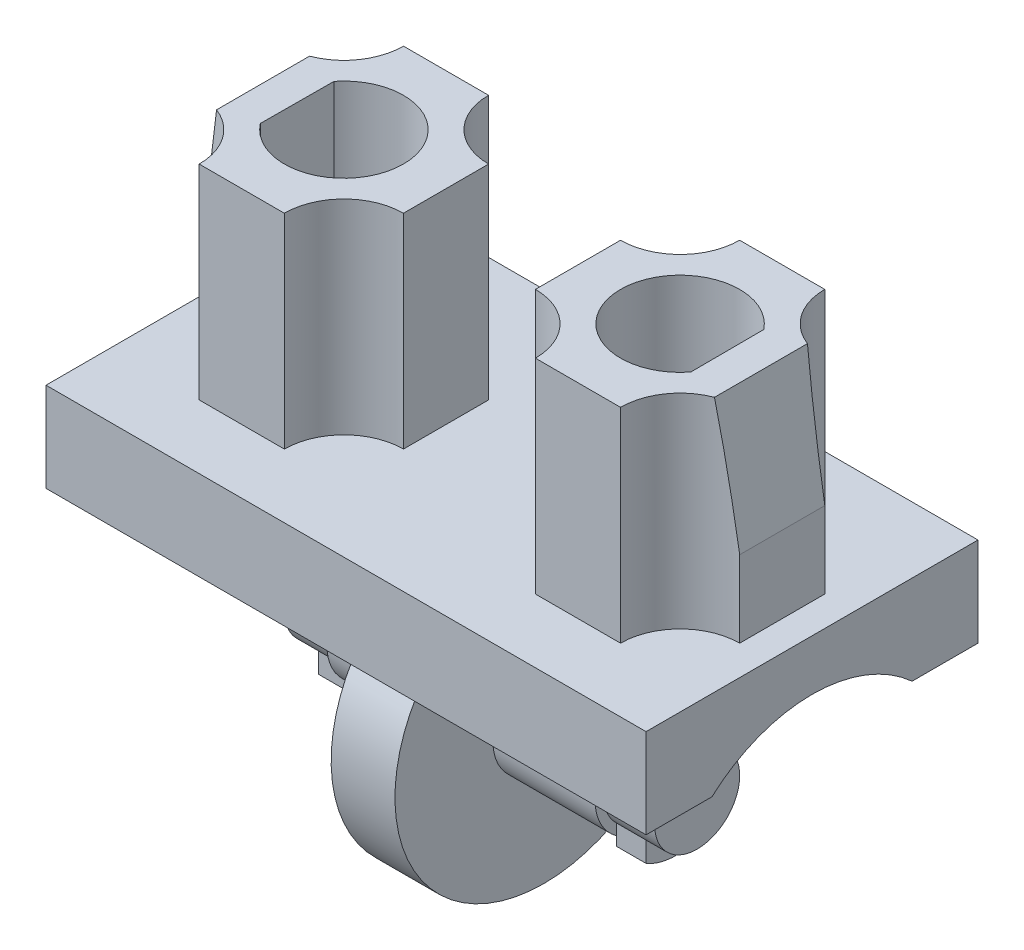
SolidWorks part; units mm, degrees
ref_plane "Front Plane" through (0, 0, 0) normal (0, 0, 1) x (1, 0, 0)
ref_plane "Top Plane" through (0, 0, 0) normal (0, 1, 0) x (1, 0, 0)
ref_plane "Right Plane" through (0, 0, 0) normal (1, 0, 0) x (0, 0, -1)
sketch "Sketch1" plane through (0, 0, 0) normal (1, 0, 0) x (0, 0, -1)
  line L0 (0, 0) -> (0, -4.7) construction
  line L1 (2.3513, -2.1074) -> (3.9, -2.1074)
  line L2 (-3.9, -2.1074) -> (-2.3513, -2.1074)
  line L3 (-3.9, -2.1074) -> (-3.9, -0.0074)
  line L4 (-3.9, -0.0074) -> (3.9, -0.0074)
  line L5 (3.9, -2.1074) -> (3.9, -0.0074)
  line L6 (-3.9, -2.1074) -> (3.9, -0.0074) construction
  line L7 (-3.9, -0.0074) -> (3.9, -2.1074) construction
  circle A0 centre (0, -4.7) radius 3.5
  point P3 (0, -1.0574)
  point P9 (0, -0.9349)
  point P10 (0, -4.7)
  dimension "D2" = 7
  dimension "D1" = 4.7
  dimension "D3" = 7.8
  dimension "D4" = 2.1
extrude "Hip Base - Extruded Boss/Base" add sketch "Sketch1" along normal mid plane 14.1 contours A0 L1 L5 L4 L3 L2 region at (0, -0.9088, 0)
extrude "Leg Joint - Extruded Boss/Base" add sketch "Sketch1<3>" along normal mid plane 1.5 contours A0 region at (0, -4.7, 0)
sketch "Sketch1<3>" plane through (0, 0, 0) normal (1, 0, 0) x (0, 0, -1) same geometry as "Sketch1"
sketch "Sketch2" plane through (0.75, 0, 0) normal (1, 0, 0) x (0, 0, -1)
  circle A0 centre (0, -4.7) radius 1.2
  dimension "D1" = 2.4
extrude "Leg Peg - Extruded Boss/Base" add sketch "Sketch2" along normal blind 2.4
sketch "Sketch3" plane through (3.15, 0, 0) normal (1, 0, 0) x (0, 0, -1)
  line L0 (-0.6614, -3.95) -> (0.6614, -3.95)
  arc A0 (-0.6614, -3.95) -> (0.6614, -3.95) centre (0, -4.7) ccw
  dimension "D1" = 2
  dimension "D2" = 0.75
extrude "Leg Peg Inner - Extruded Boss/Base" add sketch "Sketch3" along normal blind 1.2
sketch "Sketch4" plane through (3.15, 0, 0) normal (1, 0, 0) x (0, 0, -1)
  line L2 (-0.7, -5.8893) -> (-0.7, -5.4141)
  line L4 (0.7, -5.8893) -> (0.7, -5.4141)
  arc A0 (-0.6614, -3.95) -> (0.6614, -3.95) centre (0, -4.7) ccw construction
  circle A1 centre (0, -4.7) radius 1.2
  arc A2 (-0.7, -5.6747) -> (0.7, -5.6747) centre (0, -4.7) ccw
  arc A3 (-0.7, -5.4141) -> (0.7, -5.4141) centre (0, -4.7) ccw
  arc A4 (-0.7, -5.8893) -> (0.7, -5.8893) centre (0, -4.7) ccw
  arc A5 (-0.6614, -3.95) -> (0.6614, -3.95) centre (0, -4.7) ccw construction
  arc A6 (-0.9128, -3.665) -> (0.9128, -3.665) centre (0, -4.7) ccw construction
  point P10 (0, 0)
  point P15 (0.7, -5.4313)
  dimension "D3" = 0.7
  dimension "D4" = 1.4
  dimension "D1" = 0
  dimension "D2" = 0.38
extrude "Leg Lock - Extruded Detail" add sketch "Sketch4" along normal blind 0.7 contours L2 A3 L4 A4
sketch "Sketch5" plane through (0, -0.0074, 0) normal (0, 1, 0) x (1, 0, 0)
  line L0 (0, 0) -> (7.05, 0) construction
  line L1 (7.05, -3.9) -> (7.05, 3.9) construction
  line L3 (1.55, -2.4) -> (6.35, -2.4)
  line L4 (1.55, -2.4) -> (1.55, 2.4)
  line L5 (1.55, 2.4) -> (6.35, 2.4)
  line L6 (6.35, -2.4) -> (6.35, 2.4)
  line L7 (1.55, -2.4) -> (6.35, 2.4) construction
  line L8 (1.55, 2.4) -> (6.35, -2.4) construction
  circle A0 centre (1.55, 2.4) radius 1.4
  circle A1 centre (6.35, 2.4) radius 1.4
  circle A2 centre (6.35, -2.4) radius 1.4
  circle A3 centre (1.55, -2.4) radius 1.4
  point P5 (3.95, 0)
  point P11 (0, 0)
  point P20 (3.95, 0)
  dimension "D4" = 2.8
  dimension "D1" = 1.55
  dimension "D2" = 4.8
  dimension "D3" = 4.8
  dimension "D5" = 4
extrude "Hip Peg - Extruded Boss/Base" add sketch "Sketch5" along normal blind 4.8 contours A3 L3 A2 L6 A1 L5 A0 L4 region at (3.95, -0.0074, 0)
sketch "Sketch6" plane through (0, 4.7926, 0) normal (0, 1, 0) x (1, 0, 0)
  line L0 (4.95, 2.4) -> (2.95, -2.4) construction
  line L1 (5.058, -0.8557) -> (5.05, 0.866)
  arc A0 (5.05, 0.866) -> (5.058, -0.8557) centre (3.95, 0) ccw
  point P8 (5.04, 0.8785)
  point P9 (4.95, -0.8705)
  point P10 (5.182, -0.8567)
  point P11 (5.04, -0.8785)
  dimension "D1" = 2.8
  dimension "D2" = 1.3
extrude "Hip Cavity - Extruded Cut" cut sketch "Sketch6" against normal up to surface (4.8 mm away) up to face at (3.95, -0.0074, 0)
sketch "Sketch7" plane through (0, 0, 0) normal (0, 0, 1) x (1, 0, 0)
  line L0 (6.35, 4.7926) -> (6.35, 1.7926)
  line L1 (6.35, 4.7926) -> (6.35, -0.0074) construction
  line L2 (6.35, 1.7926) -> (5.85, 4.7926)
  line L3 (6.35, 4.7926) -> (4.95, 4.7926) construction
  line L4 (5.85, 4.7926) -> (6.35, 4.7926)
  dimension "D1" = 0.5
  dimension "D2" = 3
extrude "Hip Peg Chamfer" cut sketch "Sketch7" against normal through all both and the other way through all
mirror "Mirror1" about plane through (0, 0, 0) normal (1, 0, 0) of "Hip Peg Chamfer", "Hip Cavity - Extruded Cut", "Hip Peg - Extruded Boss/Base", "Leg Lock - Extruded Detail", "Leg Peg Inner - Extruded Boss/Base", "Leg Peg - Extruded Boss/Base"
